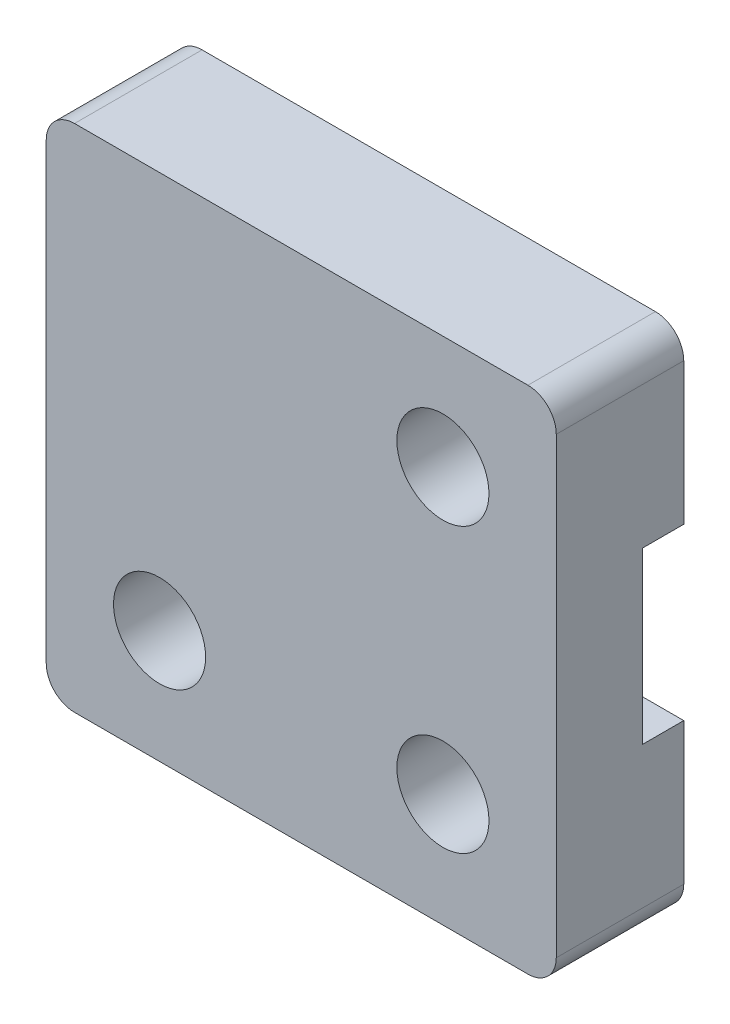
SolidWorks part; units mm, degrees
ref_plane "Front Plane" through (0, 0, 0) normal (0, 0, 1) x (1, 0, 0)
ref_plane "Top Plane" through (0, 0, 0) normal (0, 1, 0) x (1, 0, 0)
ref_plane "Right Plane" through (0, 0, 0) normal (1, 0, 0) x (0, 0, -1)
sketch "Sketch1" plane through (0, 0, 0) normal (0, 0, 1) x (1, 0, 0)
  line L0 (14, 14) -> (14, 4) construction
  line L1 (0, 0) -> (18, 0)
  line L2 (0, 0) -> (0, 18)
  line L3 (0, 18) -> (18, 18)
  line L4 (18, 0) -> (18, 18)
  line L5 (14, 4) -> (4, 4) construction
  circle A0 centre (4, 4) radius 1.625
  circle A1 centre (14, 4) radius 1.625
  circle A2 centre (14, 14) radius 1.625
  dimension "D1" = 3.25
  dimension "D2" = 18
  dimension "D3" = 10
  dimension "D4" = 4
  dimension "D5" = 4
extrude "Boss-Extrude1" add sketch "Sketch1" along normal blind 4
sketch "Sketch2" plane through (0, 0, 0) normal (0, 0, -1) x (-1, 0, 0)
  line L0 (-18, 0) -> (-18, 18) construction
  line L1 (-18, 12) -> (-17, 12)
  line L2 (-18, 12) -> (-18, 6)
  line L3 (-18, 6) -> (-17, 6)
  line L4 (-17, 12) -> (-17, 6)
  line L5 (-16, 12) -> (-16, 6)
  line L6 (-17, 12) -> (-16, 12)
  line L7 (-17, 12) -> (-17, 6)
  line L8 (-17, 6) -> (-16, 6)
  line L9 (-15, 12) -> (-15, 6)
  line L10 (-16, 12) -> (-15, 12)
  line L11 (-16, 12) -> (-16, 6)
  line L12 (-16, 6) -> (-15, 6)
  line L13 (-14, 12) -> (-14, 6)
  line L14 (-15, 12) -> (-14, 12)
  line L15 (-15, 12) -> (-15, 6)
  line L16 (-15, 6) -> (-14, 6)
  line L17 (-13, 12) -> (-13, 6)
  line L18 (-14, 12) -> (-13, 12)
  line L19 (-14, 12) -> (-14, 6)
  line L20 (-14, 6) -> (-13, 6)
  line L21 (-12, 12) -> (-12, 6)
  line L22 (-13, 12) -> (-12, 12)
  line L23 (-13, 12) -> (-13, 6)
  line L24 (-13, 6) -> (-12, 6)
  line L25 (-11, 12) -> (-11, 6)
  line L26 (-12, 12) -> (-11, 12)
  line L27 (-12, 12) -> (-12, 6)
  line L28 (-12, 6) -> (-11, 6)
  line L29 (-10, 12) -> (-10, 6)
  line L30 (-11, 12) -> (-10, 12)
  line L31 (-11, 12) -> (-11, 6)
  line L32 (-11, 6) -> (-10, 6)
  line L33 (-9, 12) -> (-9, 6)
  line L34 (-10, 12) -> (-9, 12)
  line L35 (-10, 12) -> (-10, 6)
  line L36 (-10, 6) -> (-9, 6)
  line L37 (-8, 12) -> (-8, 6)
  line L38 (-9, 12) -> (-8, 12)
  line L39 (-9, 12) -> (-9, 6)
  line L40 (-9, 6) -> (-8, 6)
  line L41 (-7, 12) -> (-7, 6)
  line L42 (-8, 12) -> (-7, 12)
  line L43 (-8, 12) -> (-8, 6)
  line L44 (-8, 6) -> (-7, 6)
  line L45 (-6, 12) -> (-6, 6)
  line L46 (-7, 12) -> (-6, 12)
  line L47 (-7, 12) -> (-7, 6)
  line L48 (-7, 6) -> (-6, 6)
  line L49 (-5, 12) -> (-5, 6)
  line L50 (-6, 12) -> (-5, 12)
  line L51 (-6, 12) -> (-6, 6)
  line L52 (-6, 6) -> (-5, 6)
  line L53 (-4, 12) -> (-4, 6)
  line L54 (-5, 12) -> (-4, 12)
  line L55 (-5, 12) -> (-5, 6)
  line L56 (-5, 6) -> (-4, 6)
  line L57 (-3, 12) -> (-3, 6)
  line L58 (-4, 12) -> (-3, 12)
  line L59 (-4, 12) -> (-4, 6)
  line L60 (-4, 6) -> (-3, 6)
  line L61 (-2, 12) -> (-2, 6)
  line L62 (-3, 12) -> (-2, 12)
  line L63 (-3, 12) -> (-3, 6)
  line L64 (-3, 6) -> (-2, 6)
  line L65 (-1, 12) -> (-1, 6)
  line L66 (-2, 12) -> (-1, 12)
  line L67 (-2, 12) -> (-2, 6)
  line L68 (-2, 6) -> (-1, 6)
  line L69 (0, 12) -> (0, 6)
  line L70 (-1, 12) -> (0, 12)
  line L71 (-1, 12) -> (-1, 6)
  line L72 (-1, 6) -> (0, 6)
  line M7 (-18, 18) -> (-18, 0)
  dimension "D1" = 6
  dimension "D2" = 1
  dimension "D3" = 6
  dimension "D4" = 18
extrude "Cut-Extrude1" cut sketch "Sketch2" against normal blind 0.95 contours L4 L1 L3 M7 | L5 L12 L9 L10 | L13 L20 L17 L18 | L21 L28 L25 L26 | L29 L36 L33 L34 | L37 L44 L41 L42 | L45 L52 L49 L50 | L53 L60 L57 L58 | L61 L68 L65 L66 region at (17.5, 9, 0) region at (15.5, 9, 0) region at (13.5, 9, 0) region at (11.5, 9, 0) region at (9.5, 9, 0) region at (7.5, 9, 0) region at (5.5, 9, 0) region at (3.5, 9, 0) region at (1.5, 9, 0)
sketch "Sketch3" plane through (0, 0, 0) normal (0, 0, -1) x (-1, 0, 0)
  line L0 (0, 18) -> (0, 0) construction
  line L1 (-18, 18) -> (0, 18)
  line L2 (-18, 18) -> (-18, 12)
  line L3 (-18, 12) -> (0, 12)
  line L4 (-2, 12) -> (-2, 6)
  line L5 (-1, 12) -> (-2, 12)
  line L6 (-1, 6) -> (-1, 12)
  line L7 (-2, 6) -> (-1, 6)
  line L8 (-2, 12) -> (-2, 6)
  line L9 (-1, 12) -> (-2, 12)
  line L10 (-1, 6) -> (-1, 12)
  line L11 (-2, 6) -> (-1, 6)
  line L12 (-4, 12) -> (-4, 6)
  line L13 (-3, 12) -> (-4, 12)
  line L14 (-3, 6) -> (-3, 12)
  line L15 (-4, 6) -> (-3, 6)
  line L16 (-4, 12) -> (-4, 6)
  line L17 (-3, 12) -> (-4, 12)
  line L18 (-3, 6) -> (-3, 12)
  line L19 (-4, 6) -> (-3, 6)
  line L20 (-6, 12) -> (-6, 6)
  line L21 (-5, 12) -> (-6, 12)
  line L22 (-5, 6) -> (-5, 12)
  line L23 (-6, 6) -> (-5, 6)
  line L24 (-6, 12) -> (-6, 6)
  line L25 (-5, 12) -> (-6, 12)
  line L26 (-5, 6) -> (-5, 12)
  line L27 (-6, 6) -> (-5, 6)
  line L28 (-8, 12) -> (-8, 6)
  line L29 (-7, 12) -> (-8, 12)
  line L30 (-7, 6) -> (-7, 12)
  line L31 (-8, 6) -> (-7, 6)
  line L32 (-8, 12) -> (-8, 6)
  line L33 (-7, 12) -> (-8, 12)
  line L34 (-7, 6) -> (-7, 12)
  line L35 (-8, 6) -> (-7, 6)
  line L36 (-10, 12) -> (-10, 6)
  line L37 (-9, 12) -> (-10, 12)
  line L38 (-9, 6) -> (-9, 12)
  line L39 (-10, 6) -> (-9, 6)
  line L40 (-10, 12) -> (-10, 6)
  line L41 (-9, 12) -> (-10, 12)
  line L42 (-9, 6) -> (-9, 12)
  line L43 (-10, 6) -> (-9, 6)
  line L44 (-12, 12) -> (-12, 6)
  line L45 (-11, 12) -> (-12, 12)
  line L46 (-11, 6) -> (-11, 12)
  line L47 (-12, 6) -> (-11, 6)
  line L48 (-12, 12) -> (-12, 6)
  line L49 (-11, 12) -> (-12, 12)
  line L50 (-11, 6) -> (-11, 12)
  line L51 (-12, 6) -> (-11, 6)
  line L52 (-14, 12) -> (-14, 6)
  line L53 (-13, 12) -> (-14, 12)
  line L54 (-13, 6) -> (-13, 12)
  line L55 (-14, 6) -> (-13, 6)
  line L56 (-14, 12) -> (-14, 6)
  line L57 (-13, 12) -> (-14, 12)
  line L58 (-13, 6) -> (-13, 12)
  line L59 (-14, 6) -> (-13, 6)
  line L60 (-16, 12) -> (-16, 6)
  line L61 (-15, 12) -> (-16, 12)
  line L62 (-15, 6) -> (-15, 12)
  line L63 (-16, 6) -> (-15, 6)
  line L64 (-16, 12) -> (-16, 6)
  line L65 (-15, 12) -> (-16, 12)
  line L66 (-15, 6) -> (-15, 12)
  line L67 (-16, 6) -> (-15, 6)
  line L68 (0, 18) -> (0, 12)
  line L70 (-18, 6) -> (0, 6)
  line L71 (-18, 6) -> (-18, 0)
  line L72 (-18, 0) -> (0, 0)
  line L73 (0, 6) -> (0, 0)
  circle A1 centre (-4, 4) radius 1.625
  circle A2 centre (-4, 4) radius 1.625
  circle A3 centre (-14, 4) radius 1.625
  circle A4 centre (-14, 4) radius 1.625
  circle A5 centre (-14, 14) radius 1.625
  circle A6 centre (-14, 14) radius 1.625
  line M36 (-17, 6) -> (-18, 6)
  line M37 (-18, 6) -> (-18, 0)
  line M38 (-18, 0) -> (0, 0)
  line M39 (0, 0) -> (0, 18)
  line M40 (0, 18) -> (-18, 18)
  line M41 (-18, 18) -> (-18, 12)
  line M42 (-18, 12) -> (-17, 12)
  line M45 (-16, 12) -> (-15, 12)
  line M47 (-15, 6) -> (-16, 6)
  line M49 (-14, 12) -> (-13, 12)
  line M51 (-13, 6) -> (-14, 6)
  line M53 (-12, 12) -> (-11, 12)
  line M55 (-11, 6) -> (-12, 6)
  line M57 (-10, 12) -> (-9, 12)
  line M59 (-9, 6) -> (-10, 6)
  line M61 (-8, 12) -> (-7, 12)
  line M63 (-7, 6) -> (-8, 6)
  line M65 (-6, 12) -> (-5, 12)
  line M67 (-5, 6) -> (-6, 6)
  line M69 (-4, 12) -> (-3, 12)
  line M71 (-3, 6) -> (-4, 6)
  line M73 (-2, 12) -> (-1, 12)
  line M75 (-1, 6) -> (-2, 6)
  circle M76 centre (-14, 4) radius 1.625
  circle M77 centre (-4, 4) radius 1.625
  circle M78 centre (-14, 14) radius 1.625
  dimension "D1" = 0
  dimension "D2" = 0
  dimension "D3" = 0
  dimension "D4" = 0
  dimension "D5" = 0
  dimension "D6" = 0
  dimension "D7" = 0
  dimension "D8" = 0
  dimension "D9" = 0
  dimension "D10" = 0
  dimension "D11" = 0
extrude "Boss-Extrude2" add sketch "Sketch3" along normal blind 0.5 contours L70 M36 M37 M38 M39 M75 M71 M67 M63 M59 M55 M51 M47 M76 M77 | L3 M42 M45 M49 M53 M57 M61 M65 M69 M73 M39 M40 M41 M78 region at (8.584, 15.0832, 0) region at (9, 2.8185, 0)
fillet "Fillet1" radius 1 4 edges at (0, 0, 1.75) (18, 0, 1.75) (18, 18, 1.75) (0, 18, 1.75)
